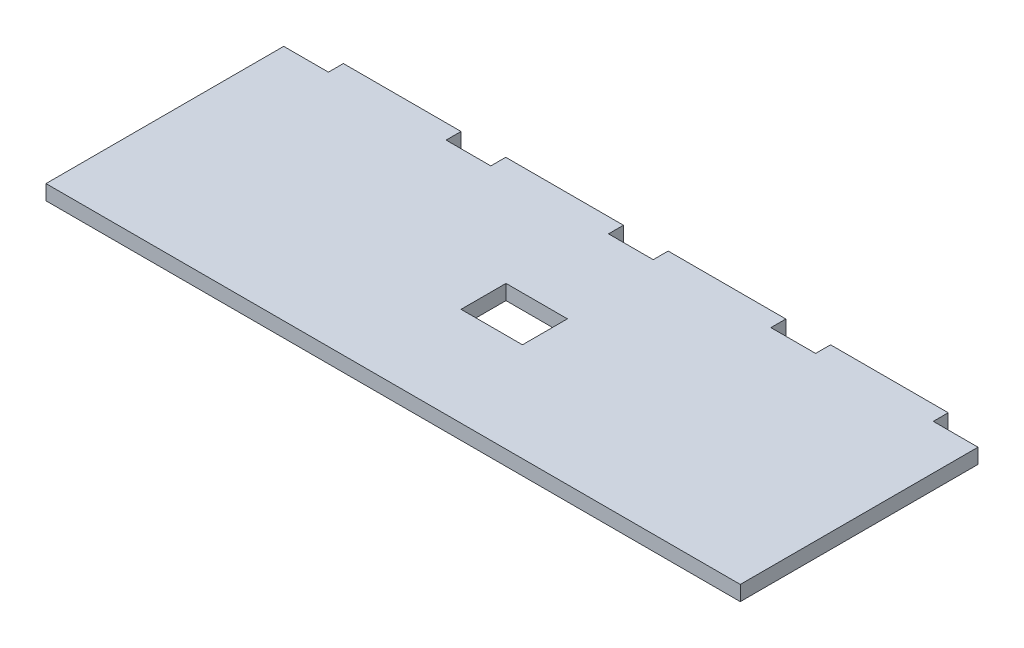
SolidWorks part; units mm, degrees
material "Beech"
ref_plane "Front Plane" through (0, 0, 0) normal (0, 0, 1) x (1, 0, 0)
ref_plane "Top Plane" through (0, 0, 0) normal (0, 1, 0) x (1, 0, 0)
ref_plane "Right Plane" through (0, 0, 0) normal (1, 0, 0) x (0, 0, -1)
sketch "Sketch1" plane through (0, 0, 0) normal (0, 1, 0) x (1, 0, 0)
  line L2 (0, 0) -> (0, -101)
  line L3 (0, -101) -> (295, -101)
  line L4 (295, 0) -> (295, -101)
  line L5 (134.45, -40) -> (160.55, -40)
  line L6 (134.45, -40) -> (134.45, -59.1)
  line L7 (134.45, -59.1) -> (160.55, -59.1)
  line L8 (160.55, -40) -> (160.55, -59.1)
  line L24 (0, 0) -> (19, 0)
  line L45 (19, 0) -> (19, 6.35)
  line L46 (19, 6.35) -> (69, 6.35)
  line L47 (69, 0) -> (69, 6.35)
  line L48 (88, 0) -> (88, 6.35)
  line L49 (88, 6.35) -> (138, 6.35)
  line L50 (138, 0) -> (138, 6.35)
  line L52 (157, 0) -> (157, 6.35)
  line L53 (157, 6.35) -> (207, 6.35)
  line L54 (207, 0) -> (207, 6.35)
  line L56 (226, 0) -> (226, 6.35)
  line L57 (226, 6.35) -> (276, 6.35)
  line L58 (276, 0) -> (276, 6.35)
  line L59 (69, 0) -> (88, 0)
  line L60 (207, 0) -> (226, 0)
  line L61 (276, 0) -> (295, 0)
  line L62 (138, 0) -> (157, 0)
  dimension "D1" = 295
  dimension "D2" = 101
  dimension "D3" = 40
  dimension "D4" = 19.1
  dimension "D5" = 134.45
  dimension "D6" = 6.35
  dimension "D7" = 50
  dimension "D8" = 19
  dimension "D9" = 4
  dimension "D11" = 26.1
  dimension "D10" = 19
extrude "Boss-Extrude1" add sketch "Sketch1" along normal blind 6.35
